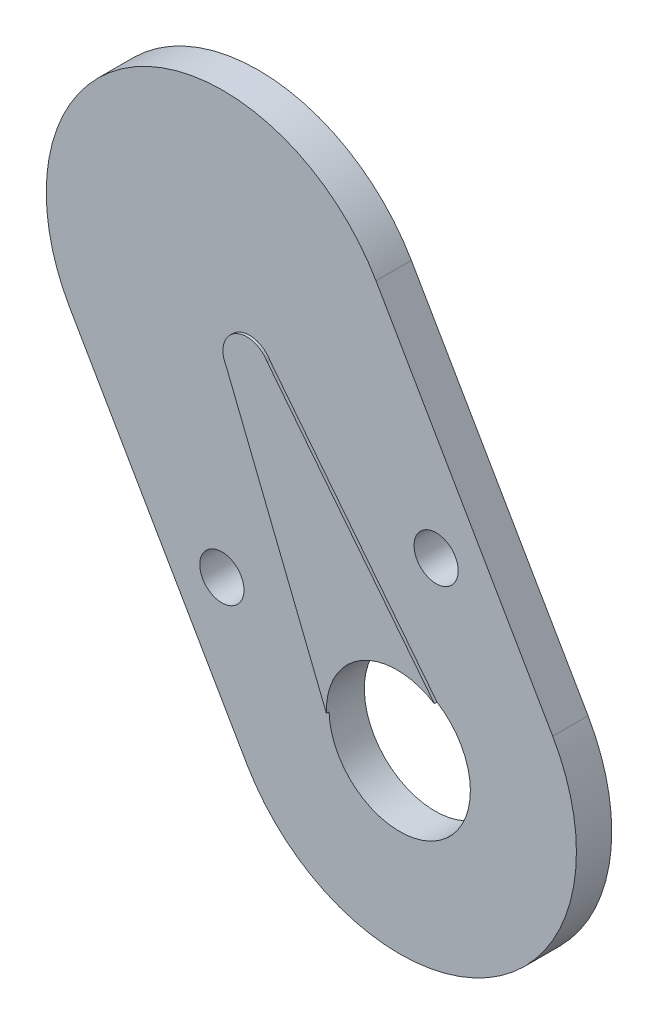
SolidWorks part; units mm, degrees
ref_plane "前视基准面" through (0, 0, 0) normal (0, 0, 1) x (1, 0, 0)
ref_plane "上视基准面" through (0, 0, 0) normal (0, 1, 0) x (1, 0, 0)
ref_plane "右视基准面" through (0, 0, 0) normal (1, 0, 0) x (0, 0, -1)
other "Configuration Table"
sketch "草图1" plane through (0, 0, 0) normal (0, 0, 1) x (1, 0, 0)
  line L0 (8.6603, 5) -> (-1.3397, 22.3205)
  line L1 (-1.3397, 22.3205) -> (-18.6603, 12.3205)
  line L2 (-18.6603, 12.3205) -> (-8.6603, -5)
  line L3 (-8.6603, -5) -> (8.6603, 5)
extrude "Retainer_plate_2mm" add sketch "草图1" along normal blind 2 from offset 2 offset against normal yes
sketch "草图2" plane through (0, 0, 0) normal (0, 0, 1) x (1, 0, 0)
  circle A0 centre (0, 0) radius 10
extrude "Retainer_plate_2mm_root" add sketch "草图2" along normal blind 2 from offset 2 offset against normal yes
sketch "草图3" plane through (0, 0, 0) normal (0, 0, 1) x (1, 0, 0)
  circle A0 centre (-10, 17.3205) radius 10
extrude "Retainer_plate_2mm_tip" add sketch "草图3" along normal blind 2 from offset 2 offset against normal yes
sketch "草图4" plane through (0, 0, 0) normal (0, 0, 1) x (1, 0, 0)
  line L0 (3.2909, 1.9) -> (-7.3309, 15.3974)
  line L1 (-7.3309, 15.3974) -> (-9.6691, 14.0474)
  line L2 (-9.6691, 14.0474) -> (-3.2909, -1.9)
  line L3 (-3.2909, -1.9) -> (3.2909, 1.9)
extrude "Horn_contact_pad_0p15" add sketch "草图4" along normal blind 0.15 from offset 0
sketch "草图5" plane through (0, 0, 0) normal (0, 0, 1) x (1, 0, 0)
  circle A0 centre (0, 0) radius 3.8
extrude "Horn_contact_pad_0p15_root" add sketch "草图5" along normal blind 0.15 from offset 0
sketch "草图6" plane through (0, 0, 0) normal (0, 0, 1) x (1, 0, 0)
  circle A0 centre (-8.5, 14.7224) radius 1.35
extrude "Horn_contact_pad_0p15_tip" add sketch "草图6" along normal blind 0.15 from offset 0
sketch "草图7" plane through (0, 0, 0) normal (0, 0, 1) x (1, 0, 0)
  circle A0 centre (0, 0) radius 4
extrude "Boss_clearance_8" cut sketch "草图7" along normal blind 2.5 from offset 2.1 offset against normal yes
sketch "草图8" plane through (0, 0, 0) normal (0, 0, 1) x (1, 0, 0)
  circle A0 centre (2.0622, 10.4282) radius 1.25
  circle A1 centre (-10.0622, 3.4282) radius 1.25
extrude "M2_clearance_2p5_pitch14" cut sketch "草图8" along normal blind 2.5 from offset 2.1 offset against normal yes
